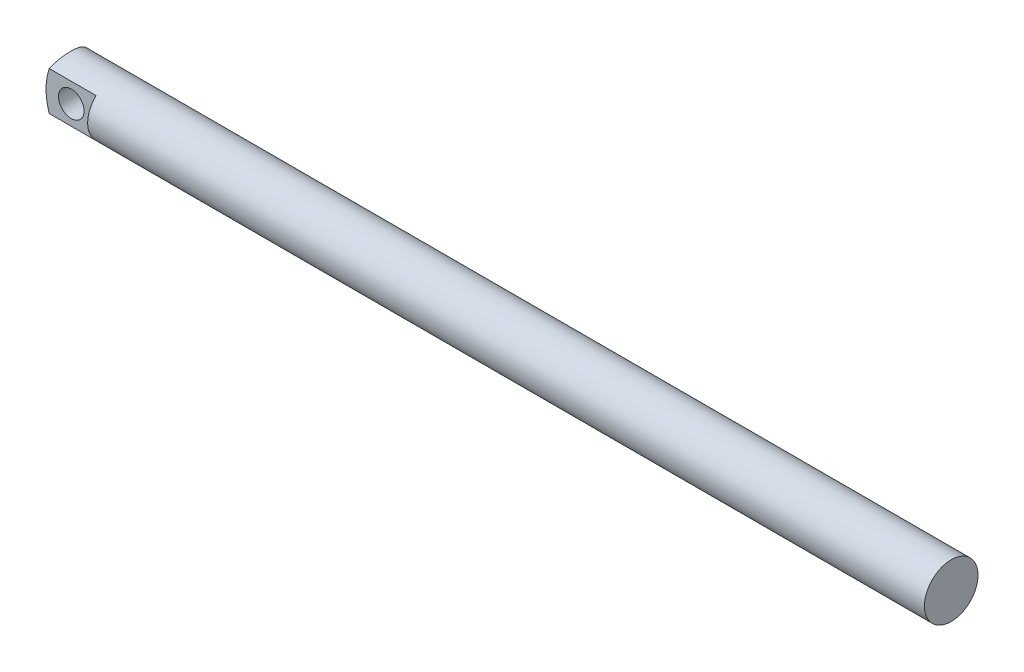
SolidWorks part; units mm, degrees
ref_plane "Front Plane" through (0, 0, 0) normal (0, 0, 1) x (1, 0, 0)
ref_plane "Top Plane" through (0, 0, 0) normal (0, 1, 0) x (1, 0, 0)
ref_plane "Right Plane" through (0, 0, 0) normal (1, 0, 0) x (0, 0, -1)
sketch "Sketch1" plane through (0, 0, 0) normal (0, 0, 1) x (1, 0, 0)
  line L0 (0, 8.9) -> (0, 9.4)
  line L1 (0, 0) -> (139, 0)
  line L2 (0, 0) -> (0, 8.9)
  line L3 (0, 8.9) -> (139, 8.9)
  line L4 (139, 0) -> (139, 8.9)
  line L5 (0, -55) -> (0, 55) construction
  line L6 (0, 9.4) -> (-7.0089, 9.4)
  line L7 (-7.0089, -0.5) -> (0, -0.5)
  line L8 (0, -0.5) -> (0, 0)
  line L9 (0, 4.45) -> (-1.8787, 4.45) construction
  line L10 (0, 9.4) -> (0, 8.9)
  line L11 (-2, 4.45) -> (0, 4.45) construction
  line L12 (-1, 4.45) -> (-1, 7.45)
  line L13 (-1, 4.45) -> (-1, 1.45)
  line L14 (-1, 4.45) -> (0, 4.45)
  arc A0 (-7.0089, 9.4) -> (-7.0089, -0.5) centre (1.68, 4.45) ccw
  circle A1 centre (-4.125, 4.45) radius 2.125
  point P20 (-6.25, 4.45)
  point P22 (-8.32, 4.45)
  dimension "D3" = 4.25
  dimension "D7" = 10
  dimension "D4" = 2.07
  dimension "D1" = 139
  dimension "D2" = 8.9
  dimension "D5" = 3
  dimension "D6" = 0.5
  dimension "D8" = 1
extrude "Boss-Extrude1" add sketch "Sketch1" along normal mid plane 9 contours L1 L4 L3 L2 region at (69.5, 4.45, 0)
extrude "Boss-Extrude2" add sketch "Sketch1<3>" along normal mid plane 6 contours L6 A0 L7 L8 L2 L0 A1 region at (-0.1293, 6.675, 0)
sketch "Sketch1<3>" plane through (0, 0, 0) normal (0, 0, 1) x (1, 0, 0) same geometry as "Sketch1"
sketch "Sketch2" plane through (139, 0, 0) normal (1, 0, 0) x (0, 0, -1)
  line L0 (0, 8.9) -> (-4.4, 4.45) construction
  line L1 (-4.5, 8.9) -> (4.5, 8.9) construction
  line L3 (-4.4, 4.45) -> (0.05, 4.45) construction
  line L4 (4.5, 4.45) -> (4.5, 0)
  line L5 (4.5, 0) -> (0.05, 0)
  line L6 (0.05, 0) -> (-4.5, 0)
  line L7 (-4.5, 0) -> (-4.4, 4.45)
  line L8 (-4.4, 4.45) -> (-4.4, 8.9)
  line L9 (-4.4, 8.9) -> (0, 8.9)
  line L10 (0, 8.9) -> (4.5, 8.9)
  line L11 (4.5, 8.9) -> (4.5, 4.45)
  circle A0 centre (0.05, 4.45) radius 4.45
  point P11 (14.5305, 5.4543)
  line M1 (4.5, 0) -> (4.5, 8.9)
  line M2 (4.5, 8.9) -> (-4.5, 8.9)
  line M3 (-4.5, 8.9) -> (-4.5, 0)
  line M4 (-4.5, 0) -> (4.5, 0)
extrude "Cut-Extrude1" cut sketch "Sketch2" against normal mid plane 400 contours A0 M4 M1 | A0 M3 M4 | A0 M1 M2 | A0 M2 M3 region at (139, 7.906, -3.506) region at (139, 0.994, -3.506) region at (139, 1.0183, 3.4571) region at (139, 7.906, 3.406)
sketch "Sketch5" plane through (0, 0, -3) normal (0, 0, -1) x (-1, 0, 0)
  line L0 (7.2753, 8.9) -> (0, 8.9)
  line L1 (0, 8.9) -> (-1.5365, 9.4426)
  line L2 (-1.5365, 9.4426) -> (6.7713, 9.7828)
  line L5 (6.7713, 9.7828) -> (7.2753, 8.9)
extrude "Cut-Extrude4" cut sketch "Sketch5" against normal mid plane 400
sketch "Sketch6" plane through (0, 0, 3) normal (0, 0, 1) x (1, 0, 0)
  line L0 (0, 0) -> (0.7159, -1.193)
  line L1 (0.7159, -1.193) -> (-7.9337, -1.4008)
  line L2 (-7.9337, -1.4008) -> (-7.2753, 0)
  line L3 (-7.2753, 0) -> (0, 0)
extrude "Cut-Extrude5" cut sketch "Sketch6" against normal mid plane 400
sketch "Sketch7" plane through (0, 0, 3) normal (0, 0, 1) x (1, 0, 0)
  line L0 (-7.2753, 8.9) -> (-6.8065, 9.626)
  line L1 (-6.8065, 9.626) -> (-7.2075, 9.626)
  line L2 (-7.2075, 9.626) -> (-7.2753, 8.9)
extrude "Cut-Extrude6" cut sketch "Sketch7" against normal mid plane 400
sketch "Sketch8" plane through (139, 0, 0) normal (1, 0, 0) x (0, 0, -1)
  line L0 (-4.4, 4.45) -> (-4.4972, 0.1234)
  line L1 (-5.5257, -1.4097) -> (-10.6678, 2.2804)
  line L2 (-10.6678, 2.2804) -> (-5.5257, 10.6598)
  line L3 (-5.5257, 10.6598) -> (-2.6973, 11.337)
  line L4 (-2.6973, 11.337) -> (-4.4, 7.7081)
  line L5 (-4.4, 8.9) -> (-4.4, 4.45) construction
  line L6 (-4.4, 7.7081) -> (-4.4, 4.45)
  line L7 (-4.4, 4.45) -> (-4.5, 0) construction
  line L8 (-4.4972, 0.1234) -> (-4.4972, -0.9931)
  line L9 (-4.4972, -0.9931) -> (-5.5257, -1.4097)
extrude "Cut-Extrude8" cut sketch "Sketch8" against normal mid plane 722
